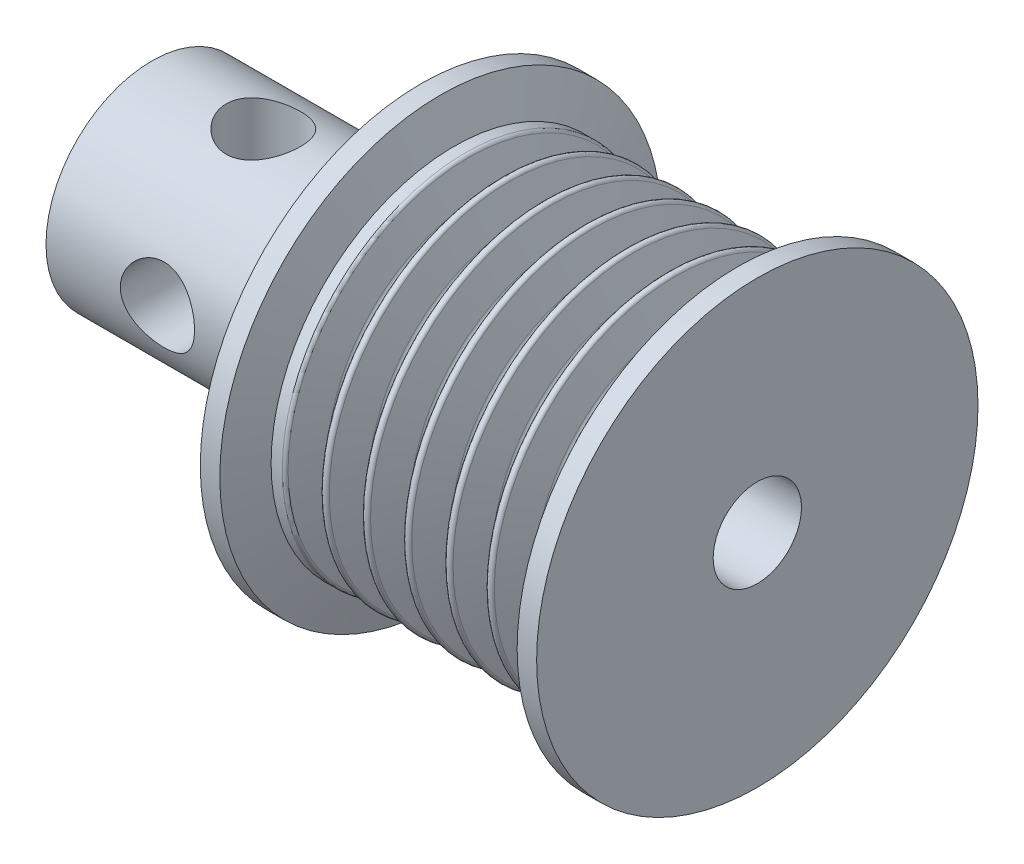
SolidWorks part; units mm, degrees
material "6061-T6 (SS)"
ref_plane "Front Plane" through (0, 0, 0) normal (0, 0, 1) x (1, 0, 0)
ref_plane "Top Plane" through (0, 0, 0) normal (0, 1, 0) x (1, 0, 0)
ref_plane "Right Plane" through (0, 0, 0) normal (1, 0, 0) x (0, 0, -1)
sketch "Sketch1" plane through (0, 0, 0) normal (0, 0, 1) x (1, 0, 0)
  line L0 (0, 0) -> (0, 2.5) construction
  line L1 (0, 2.5) -> (34.29, 2.5)
  line L2 (34.29, 2.5) -> (34.29, 12.5)
  line L3 (34.29, 12.5) -> (15.24, 12.5)
  line L4 (15.24, 12.5) -> (15.24, 6)
  line L5 (0, 0) -> (13.5959, 0) construction
  line L8 (15.24, 6) -> (0, 6)
  line L9 (0, 6) -> (0, 2.5)
  dimension "D1" = 25
  dimension "D3" = 19.05
  dimension "D6" = 12
  dimension "D7" = 15.24
revolve "Revolve1" add sketch "Sketch1" angle 360 about L5
sketch "Sketch2" plane through (0, 0, 0) normal (0, 0, 1) x (1, 0, 0)
  line L0 (29.4386, 12.5) -> (29.4386, 10.3699)
  line L1 (15.24, 6) -> (15.24, -6) construction
  line L2 (29.6295, 10.2362) -> (30.2251, 8.5999)
  line L3 (30.9889, 8.5999) -> (31.5845, 10.2362)
  line L4 (31.7754, 10.3699) -> (31.7754, 12.5)
  line L5 (31.7754, 12.5) -> (29.4386, 12.5)
  line L6 (29.4386, 11.43) -> (31.7754, 11.43) construction
  line L7 (15.24, 0) -> (34.29, 0) construction
  line L8 (29.6295, 10.2362) -> (31.5845, 10.2362) construction
  line L9 (29.4386, 12.5) -> (27.1018, 12.5) construction
  line L10 (34.29, 12.5) -> (15.24, 12.5) construction
  line L11 (27.1018, 12.5) -> (24.765, 12.5) construction
  line L13 (24.765, 0) -> (24.765, 12.5) construction
  line L15 (34.29, -12.5) -> (34.29, 12.5) construction
  arc A0 (29.4386, 10.3699) -> (29.6295, 10.2362) centre (29.4386, 10.1667) cw
  arc A1 (30.2251, 8.5999) -> (30.9889, 8.5999) centre (30.607, 8.7389) ccw
  arc A2 (31.5845, 10.2362) -> (31.7754, 10.3699) centre (31.7754, 10.1667) cw
  dimension "D5" = 0.2032
  dimension "D2" = 2.3368
  dimension "D4" = 1.1938
  dimension "D6" = 40
  dimension "D7" = 11.43
revolve "Cut-Revolve1" cut sketch "Sketch2" angle 360 about L7
pattern_linear "LPattern1" count 6 spacing 2.3368 along (-1, 0, 0) of "Cut-Revolve1"
sketch "Sketch3" plane through (0, 0, 0) normal (0, 0, 1) x (1, 0, 0)
  line L0 (31.7754, 12.5) -> (33.1857, 12.5)
  line L1 (34.29, 12.5) -> (31.7754, 12.5) construction
  line L2 (33.1857, 12.5) -> (32.4104, 10.3699)
  line L3 (32.4104, 10.3699) -> (31.7754, 10.3699)
  line L4 (31.7754, 12.5) -> (31.7754, -12.5) construction
  line L5 (31.7754, 10.3699) -> (31.7754, 12.5)
  line L6 (31.7754, 10.3699) -> (31.7754, -10.3699) construction
  line L7 (30.607, 8.3325) -> (30.607, 11.4458) construction
  line L8 (24.765, 10.3699) -> (24.765, 14.7012) construction
  line L9 (17.7546, 10.3699) -> (17.7546, 12.5)
  line L10 (17.1196, 10.3699) -> (17.7546, 10.3699)
  line L11 (16.3443, 12.5) -> (17.1196, 10.3699)
  line L12 (17.7546, 12.5) -> (16.3443, 12.5)
  line L13 (0, 0) -> (26.9583, 0) construction
  arc A0 (30.2251, 8.5999) -> (30.9889, 8.5999) centre (30.607, 8.7389) ccw construction
  arc A1 (24.9559, 10.2362) -> (24.5741, 10.2362) centre (24.765, 10.1667) ccw construction
  dimension "D1" = 1.8034
  dimension "D2" = 20
revolve "Cut-Revolve2" cut sketch "Sketch3" angle 360 about L13
fillet "Fillet1" radius 0.762 1 edges at (15.24, 0, 6)
ref_plane "Plane1" through (0, 6, 0) normal (0, 1, 0) x (1, 0, 0)
hole_wizard "M5x0.8 Tapped Hole1" positions "Sketch6" profile "Sketch5" tap size "M5x0.8" standard "ANSI Metric" end condition up to next
sketch "Sketch6" plane through (0, 6, 0) normal (0, 1, 0) x (1, 0, 0)
  line L1 (6.311, 0) -> (0, 0) construction
  line L7 (9.74, 6) -> (9.74, -6) construction
  line L8 (14.478, 6) -> (0, 6) construction
  line L9 (0, -6) -> (14.478, -6) construction
  line L11 (15.24, 6.762) -> (15.24, -6.762) construction
  circle A0 centre (6.311, 0) radius 3.429 construction
  point P0 (6.311, 0)
  dimension "D1" = 6.858
  dimension "D2" = 5.5
sketch "Sketch5" plane through (6.311, 6, 0) normal (1, 0, 0) x (0, 0, 1)
  line L0 (0, 0) -> (0, 3.5)
  line L1 (0, 3.5) -> (2.1, 3.5)
  line L2 (2.1, 3.5) -> (2.1, 0)
  line L5 (2.1, 0) -> (0, 0)
  line L11 (0, -6.35) -> (0, 107.95) construction
  dimension "Thru Tap Drill Dia." = 4.2
  dimension "Thru Tap Drill Depth" = 3.5
pattern_circular "CirPattern1" count 2 over 90 about axis through (0, 0, 0) along (-1, 0, 0) of "M5x0.8 Tapped Hole1" reverse direction yes
equation "\"D2@Sketch1\"=5mm"
equation "\"D4@Sketch2\"=0.094in/2"
equation "\"D1@Sketch1\"=25mm"
equation "\"D3@Sketch1\"=0.75in"
equation "\"D7@Sketch2\"=0.9in/2"
equation "\"D7@Sketch1\"=0.60in"
equation "\"D2@Sketch6\"=5.5mm"
equation "\"D6@Sketch1\"=12mm"
